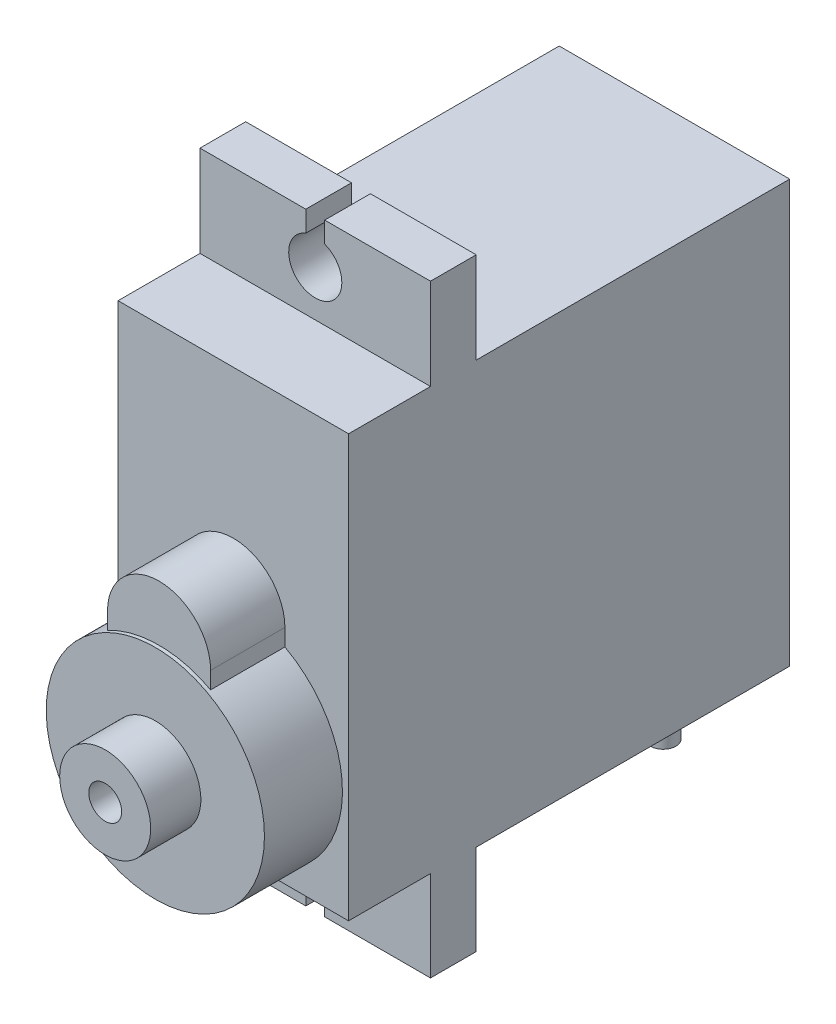
SolidWorks part; units mm, degrees
ref_plane "Front" through (0, 0, 0) normal (0, 0, 1) x (1, 0, 0)
ref_plane "Top" through (0, 0, 0) normal (0, 1, 0) x (1, 0, 0)
ref_plane "Right" through (0, 0, 0) normal (1, 0, 0) x (0, 0, -1)
sketch "Sketch1" plane through (0, 0, 0) normal (0, 1, 0) x (1, 0, 0)
  line L0 (0, 0) -> (12.41, 0)
  line L1 (12.41, 0) -> (12.41, 23.75)
  line L2 (12.41, 23.75) -> (0, 23.75)
  line L3 (0, 23.75) -> (0, 0)
  dimension "D1" = 23.75
  dimension "D2" = 12.41
extrude "Boss-Extrude1" add sketch "Sketch1" along normal blind 22.71
sketch "Sketch2" plane through (0, 0, 0) normal (0, 0, 1) x (1, 0, 0)
  line L0 (6.205, 22.71) -> (6.205, 0) construction
  line L1 (0, 22.71) -> (12.41, 22.71) construction
  line L2 (0, 0) -> (12.41, 0) construction
  circle A0 centre (6.205, 5.875) radius 5.875
  dimension "D1" = 11.75
  dimension "D2" = 5.875
extrude "Boss-Extrude3" add sketch "Sketch2" along normal blind 4.2
sketch "Sketch4" plane through (0, 0, 0) normal (0, 0, 1) x (1, 0, 0)
  line L0 (6.205, 11.5321) -> (6.205, 22.71) construction
  line L1 (0, 22.71) -> (12.41, 22.71) construction
  line L2 (0, 14.74) -> (12.41, 14.74) construction
  line L3 (0, 22.71) -> (0, 0) construction
  line L4 (12.41, 22.71) -> (12.41, 0) construction
  line L5 (3.43, 11.965) -> (3.43, 11.0533)
  line L6 (3.43, 11.0533) -> (8.98, 11.0533)
  line L7 (8.98, 11.0533) -> (8.98, 11.965)
  circle A0 centre (6.205, 5.875) radius 5.875 construction
  arc A1 (8.98, 11.965) -> (3.43, 11.965) centre (6.205, 11.965) ccw
  circle A2 centre (6.205, 5.875) radius 5.875 construction
  dimension "D2" = 5.55
  dimension "D1" = 14.74
extrude "Boss-Extrude4" add sketch "Sketch4" along normal blind 4
sketch "Sketch6" plane through (0, 0, 0) normal (0, -1, 0) x (1, 0, 0)
  line L0 (0, -4.41) -> (12.41, -4.41)
  line L1 (0, -23.75) -> (0, 0) construction
  line L2 (12.41, 0) -> (12.41, -23.75) construction
  line L3 (12.41, -4.41) -> (12.41, -6.87)
  line L4 (12.41, -6.87) -> (0, -6.87)
  line L5 (0, -6.87) -> (0, -4.41)
  line L6 (0, 0) -> (6.205, 0) construction
  dimension "D1" = 2.46
  dimension "D2" = 4.41
extrude "Boss-Extrude5" add sketch "Sketch6" along normal blind 4.87 and the other way blind 27.62
sketch "Sketch8" plane through (0, 0, -4.41) normal (0, 0, 1) x (1, 0, 0)
  line L0 (6.205, -4.87) -> (6.205, 27.62) construction
  line L1 (12.41, -4.87) -> (0, -4.87) construction
  line L3 (0, 22.71) -> (12.41, 27.62) construction
  line L4 (6.205, 11.375) -> (12.41, 11.375) construction
  line L5 (12.41, 22.71) -> (12.41, 0) construction
  line L6 (0, -4.87) -> (12.41, 0) construction
  line L10 (12.41, 27.62) -> (0, 27.62) construction
  circle A0 centre (6.205, 25.165) radius 1.43
  circle A1 centre (6.205, -2.415) radius 1.43
  dimension "D1" = 2.86
extrude "Cut-Extrude1" cut sketch "Sketch8" against normal through all
sketch "Sketch9" plane through (0, 0, -4.41) normal (0, 0, 1) x (1, 0, 0)
  line L0 (6.205, 27.62) -> (6.205, 25.165) construction
  line L2 (12.41, -4.87) -> (0, -4.87) construction
  line L3 (5.695, 27.62) -> (5.695, 25.165)
  line L4 (6.715, 27.62) -> (6.715, 25.165)
  line L5 (5.695, 25.165) -> (6.715, 25.165)
  line L6 (5.695, -2.415) -> (6.715, -2.415)
  line L7 (5.695, -2.415) -> (5.695, -4.87)
  line L8 (5.695, 27.62) -> (5.695, -4.87) construction
  line L9 (6.205, -2.415) -> (6.205, -4.87) construction
  line L10 (6.205, 27.62) -> (6.205, -4.87) construction
  line L11 (6.715, -2.415) -> (6.715, -4.87)
  line L12 (6.715, 27.62) -> (6.715, -4.87) construction
  line L13 (5.695, -4.87) -> (6.715, -4.87)
  line L14 (5.695, 27.62) -> (6.715, 27.62)
  line L15 (12.41, 27.62) -> (0, 27.62) construction
  dimension "D1" = 0.51
  dimension "D2" = 0.51
extrude "Cut-Extrude2" cut sketch "Sketch9" against normal through all
sketch "Sketch10" plane through (0, 0, 4.2) normal (0, 0, 1) x (1, 0, 0)
  circle A0 centre (6.205, 5.875) radius 2.45
  circle A1 centre (6.205, 5.875) radius 0.885
  dimension "D1" = 4.9
  dimension "D2" = 1.77
extrude "Boss-Extrude7" add sketch "Sketch10" along normal blind 2.7
sketch "Sketch12" plane through (0, 0, 0) normal (0, -1, 0) x (1, 0, 0)
  line L0 (6.205, -23.75) -> (6.205, 0) construction
  line L1 (12.41, -23.75) -> (0, -23.75) construction
  arc A0 (5.61, -22.2894) -> (6.8, -22.2894) centre (6.205, -21.95) ccw
  arc A2 (5.61, -21.6106) -> (5.61, -22.2894) centre (5.015, -21.95) ccw
  arc A3 (6.8, -22.2894) -> (6.8, -21.6106) centre (7.395, -21.95) ccw
  arc A4 (6.8, -21.6106) -> (5.61, -21.6106) centre (6.205, -21.95) ccw
  point P5 (6.205, -21.95)
  dimension "D3" = 1.8
  dimension "D1" = 2
  dimension "D2" = 2
extrude "Boss-Extrude8" add sketch "Sketch12" along normal blind 5
ref_axis "servoAxis" through (6.205, 5.875, 10.5376) along (0, 0, -1)
